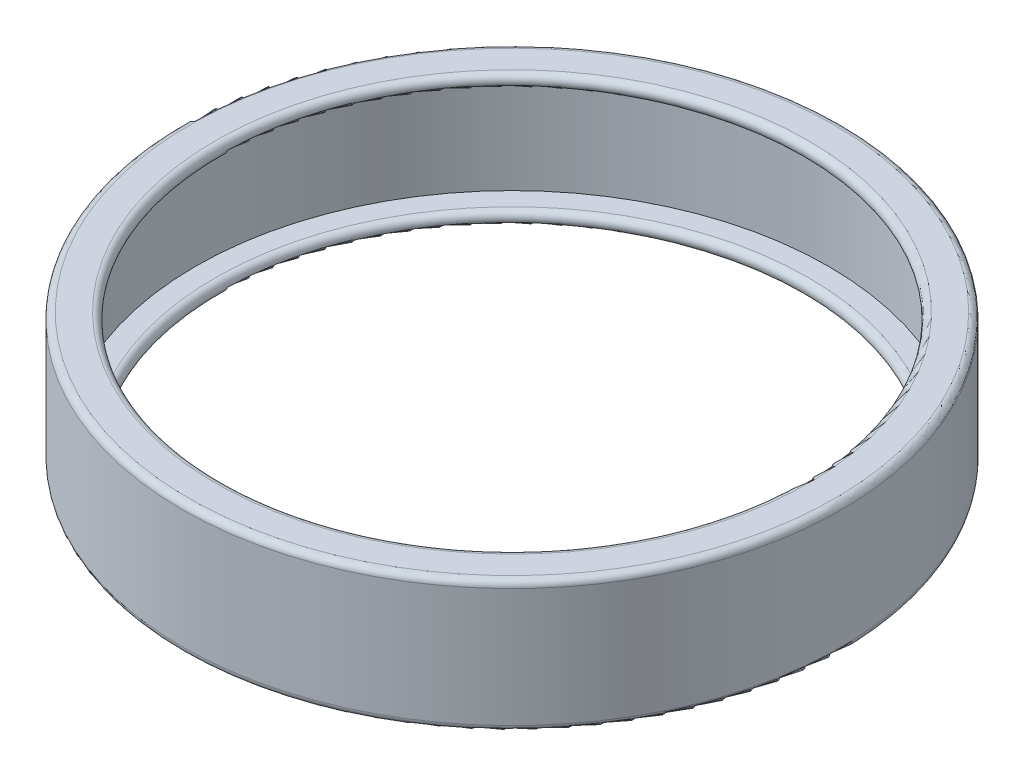
SolidWorks part; units mm, degrees
material "Chrome Stainless Steel"
ref_plane "Front Plane" through (0, 0, 0) normal (1, 0, 0) x (0, 1, 0)
ref_plane "Top Plane" through (0, 0, 0) normal (0, 0, 1) x (0, 1, 0)
ref_plane "Right Plane" through (0, 0, 0) normal (0, 1, 0) x (-1, 0, 0)
sketch "Sketch1" plane through (0, 0, 0) normal (1, 0, 0) x (0, 1, 0)
  line L0 (-15.4469, 0) -> (19.3884, 0) construction
  line L1 (0, 15.4189) -> (0, -15.0382) construction
  line L2 (-5, 22) -> (-5, 25)
  line L3 (-5, 25) -> (5, 25)
  line L4 (5, 25) -> (5, 22)
  line L5 (5, 22) -> (4, 22)
  line L6 (4, 22) -> (4, 24)
  line L7 (4, 24) -> (-4, 24)
  line L8 (-4, 24) -> (-4, 22)
  line L9 (-4, 22) -> (-5, 22)
  dimension "D1" = 10
  dimension "D2" = 8
  dimension "D3" = 1
  dimension "D4" = 1
  dimension "D5" = 50
  dimension "D6" = 1
  dimension "D7" = 44
revolve "Revolve1" add sketch "Sketch1" angle 360 about L0
fillet "Fillet1" radius 0.5 2 edges at (0, -5, -25) (0, 5, -25)
fillet "Fillet2" 2 edges at (0, 5, -22) (0, 4, -22) type full round first side face at (0, 5, -24.5) second side face at (0, 4, -22) middle face at (0, 5, -22)
fillet "Fillet3" 2 edges at (0, -5, -22) (0, -4, -22) type full round first side face at (0, -5, 24.5) second side face at (0, -4, -24) middle face at (0, -4, -22)
